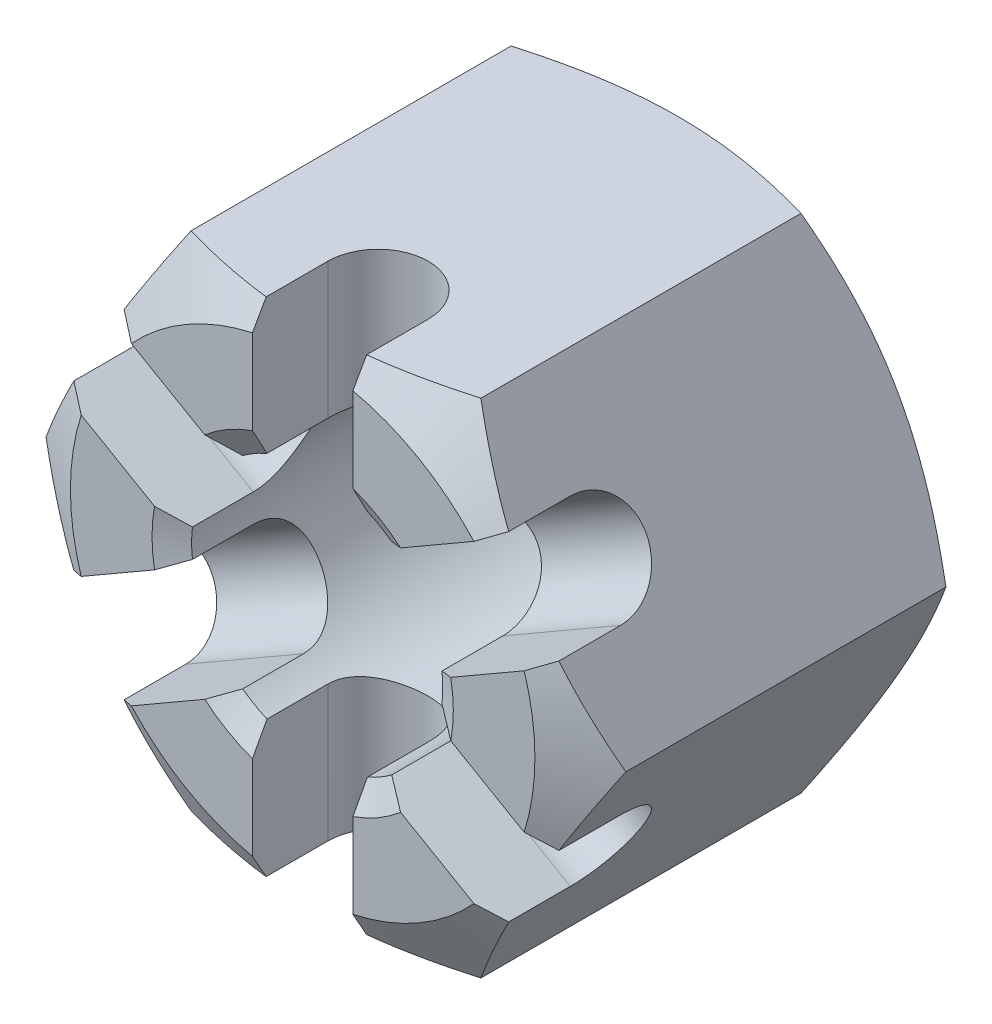
SolidWorks part; units mm, degrees
ref_plane "Front" through (0, 0, 0) normal (0, 0, 1) x (1, 0, 0)
ref_plane "Top" through (0, 0, 0) normal (0, 1, 0) x (1, 0, 0)
ref_plane "Right" through (0, 0, 0) normal (1, 0, 0) x (0, 0, -1)
sketch "Sketch1" plane through (0, 0, 0) normal (0, 0, 1) x (1, 0, 0)
  line L1 (2.8868, -5) -> (5.7735, 0)
  line L2 (5.7735, 0) -> (2.8868, 5)
  line L3 (2.8868, 5) -> (-2.8868, 5)
  line L4 (-2.8868, 5) -> (-5.7735, 0)
  line L5 (-5.7735, 0) -> (-2.8868, -5)
  line L6 (-2.8868, -5) -> (2.8868, -5)
  circle A0 centre (0, 0) radius 5 construction
  circle A1 centre (0, 0) radius 2.5
extrude "BaseNut" add sketch "Sketch1" against normal blind 7.7
cosmetic thread "ThreadCosmetic1" [suppressed] parameters "D"=6
sketch "Sketch2" plane through (0, 0, 0) normal (0, 1, 0) x (1, 0, 0)
  line L0 (-5.7735, 7.7) -> (-4.625, 7.7)
  line L2 (-4.625, 7.7) -> (-5.7735, 7.0369)
  line L3 (-5.7735, 7.0369) -> (-5.7735, 7.7)
  line L4 (0, 3.3759) -> (0, -9.8171) construction
  line L6 (-9.7712, 3.85) -> (9.8853, 3.85) construction
  line L7 (-5.7735, 0.6631) -> (-5.7735, 0)
  line L8 (-4.625, 0) -> (-5.7735, 0.6631)
  line L9 (-5.7735, 0) -> (-4.625, 0)
  dimension "D1" = 30
  dimension "D2" = 3.85
revolve "Double-Chamfer" cut sketch "Sketch2" angle 360 about L4
chamfer "EndChamfer" distance 0.5 angle 30 2 edges at (2.5, 0, -7.7) (2.5, 0, 0) first distance on face at (2.5, 0, -7.7) first distance on face at (-4.625, 0, 0)
sketch "Sketch3" plane through (0, 0, 0) normal (0, 1, 0) x (1, 0, 0)
  line L0 (0, 4.2201) -> (0, -10.5237) construction
  line L2 (-1, 0) -> (-1, 1.5)
  line L3 (1, 0) -> (1, 1.5)
  line L4 (2.7887, 7.7) -> (-2.7887, 7.7) construction
  arc A0 (-1, 1.5) -> (1, 1.5) centre (0, 1.5) cw
  point P2 (0, 2.5)
  point P3 (0, 7.7)
  dimension "W" = 5.2
  dimension "D1" = 2.5
extrude "Slot" cut sketch "Sketch3" against normal through all and the other way through all
pattern_circular "SlotPattern" count 3 over 360 about axis through (0, 0, -3.3759) along (0, 0, 1) of "Slot"
sketch "Sketch4" plane through (0, 0, 0) normal (0, 1, 0) x (1, 0, 0)
  line L0 (4.625, 0) -> (4.625, 2.5)
  line L2 (4.625, 2.5) -> (5.7735, 3.1631)
  line L4 (4.625, 0) -> (5.7735, 0)
  line L5 (5.7735, 0) -> (5.7735, 3.1631)
  line L7 (0, -0.375) -> (0, -8.8366) construction
  line L19 (4.4106, 0) -> (4.625, 0) construction
  line L20 (5.7735, 7.0369) -> (5.7735, 0.6631) construction
  dimension "D1" = 30
  dimension "W" = 5.2
revolve "Cut-Revolve1" [suppressed] cut sketch "Sketch4" angle 360 about L7
sketch "Sketch5" plane through (0, 0, 0) normal (0, 1, 0) x (1, 0, 0)
  line L0 (0, 8.5981) -> (0, -0.494) construction
  line L1 (-2.5, 7.95) -> (-2.933, 7.7)
  line L2 (-2.933, 7.7) -> (-2.5, 7.45)
  line L3 (-2.5, 7.45) -> (-2, 7.45)
  line L4 (-2, 7.45) -> (-2, 7.95)
  line L5 (-2, 7.95) -> (-2.5, 7.95)
  dimension "D1" = 0.5
  dimension "D2" = 5
revolve "Cut-Revolve10" [suppressed] cut sketch "Sketch5" angle 360 about L0
pattern_linear "LPattern10" [suppressed] count 13 spacing 0.6 along (0, 0, 1) of bodies 106
equation "\"dw@Sketch2\" = \"s@Sketch1\"-0.75"
equation "\"de@Sketch4\" = \"dw@Sketch2\""
equation "\"D1@Sketch3\" = \"m@BaseNut\" - \"W@Sketch3\""
equation "\"D2@Sketch2\" = \"m@BaseNut\" / 2"
equation "\"W@Sketch4\" = \"W@Sketch3\""
equation "\"D2@Sketch5\"=\"D@Sketch1\""
equation "\"D1@Sketch5\"= ( \"D@ThreadCosmetic1\"-\"D2@Sketch5\" )  / 2"
equation "\"D3@LPattern10\" = \"D1@Sketch5\" * 1.2"
equation "\"D1@LPattern10\" = \"m@BaseNut\" / \"D3@LPattern10\""
equation "\"D1@EndChamfer\"=\"D@Sketch1\" / 10"
